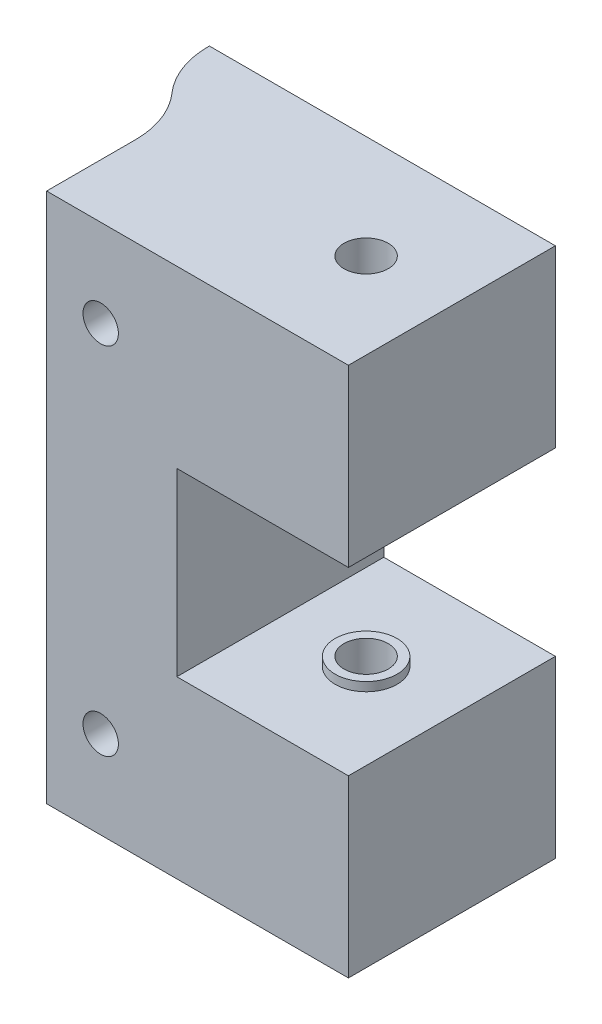
SolidWorks part; units mm, degrees
ref_plane "Front Plane" through (0, 0, 0) normal (0, 0, 1) x (1, 0, 0)
ref_plane "Top Plane" through (0, 0, 0) normal (0, 1, 0) x (1, 0, 0)
ref_plane "Right Plane" through (0, 0, 0) normal (1, 0, 0) x (0, 0, -1)
sketch "MainBlock" plane through (0, 0, 0) normal (0, 0, 1) x (1, 0, 0)
  line L0 (0, 0) -> (39.125, 0)
  line L1 (39.125, 0) -> (39.125, 19.8)
  line L2 (39.125, 19.8) -> (19.725, 19.8)
  line L3 (19.725, 19.8) -> (19.725, 40.2)
  line L4 (19.725, 40.2) -> (39.125, 40.2)
  line L5 (39.125, 40.2) -> (39.125, 60)
  line L6 (39.125, 60) -> (0, 60)
  line L7 (0, 60) -> (0, 0)
  circle A0 centre (11.1125, 50.1) radius 2
  circle A1 centre (11.1125, 9.9) radius 2
  dimension "D4" = 4
  dimension "D1" = 39.125
  dimension "D2" = 60
  dimension "D3" = 20.4
  dimension "D5" = 19.4
  dimension "D6" = 11.1125
  dimension "D7" = 9.9
  dimension "D8" = 9.9
extrude "MainBlockBoss-Extrude1" add sketch "MainBlock" along normal blind 23.4
sketch "TopHoleCut-Sketch2" plane through (0, 60, 0) normal (0, 1, 0) x (1, 0, 0)
  line L0 (39.125, 0) -> (0, 0) construction
  circle A0 centre (29.425, -11.7) radius 2.5
  dimension "D3" = 5
  dimension "D1" = 11.7
  dimension "D2" = 9.7
extrude "TopHoleCut-Extrude1" cut sketch "TopHoleCut-Sketch2" against normal blind 45
sketch "TopSpacerSketch4" plane through (0, 40.2, 0) normal (0, -1, 0) x (1, 0, 0)
  circle A0 centre (29.425, 11.7) radius 3.5
  circle A1 centre (29.425, 11.7) radius 2.5
  circle A2 centre (29.425, 11.7) radius 2.5 construction
  dimension "D1" = 7
extrude "TopSpacerBoss-Extrude2" add sketch "TopSpacerSketch4" along normal blind 1
sketch "LowerSpacerSketch5" plane through (0, 19.8, 0) normal (0, 1, 0) x (1, 0, 0)
  circle A0 centre (29.425, -11.7) radius 2.5
  circle A1 centre (29.425, -11.7) radius 2.5 construction
  circle A2 centre (29.425, -11.7) radius 3.5
  circle A3 centre (29.425, -11.7) radius 3.5 construction
extrude "LowerSpacerBoss-Extrude3" add sketch "LowerSpacerSketch5" along normal blind 1
sketch "MountHoleBoreSketch1" plane through (0, 0, 0) normal (0, 0, -1) x (-1, 0, 0)
  line L1 (-7.2375, 50.1) -> (-9.175, 53.4558)
  line L2 (-9.175, 53.4558) -> (-13.05, 53.4558)
  line L3 (-13.05, 53.4558) -> (-14.9875, 50.1)
  line L4 (-14.9875, 50.1) -> (-13.05, 46.7442)
  line L5 (-13.05, 46.7442) -> (-9.175, 46.7442)
  line L6 (-9.175, 46.7442) -> (-7.2375, 50.1)
  line L7 (-7.2375, 9.9) -> (-9.175, 13.2558)
  line L8 (-9.175, 13.2558) -> (-13.05, 13.2558)
  line L9 (-13.05, 13.2558) -> (-14.9875, 9.9)
  line L10 (-14.9875, 9.9) -> (-13.05, 6.5442)
  line L11 (-13.05, 6.5442) -> (-9.175, 6.5442)
  line L12 (-9.175, 6.5442) -> (-7.2375, 9.9)
  circle A0 centre (-11.1125, 50.1) radius 3.3558 construction
  circle A1 centre (-11.1125, 9.9) radius 3.3558 construction
  dimension "D1" = 7.75
extrude "MountHoleBoreCut-Extrude1" cut sketch "MountHoleBoreSketch1" against normal blind 2
sketch "PushPinHoleSketch1" plane through (0, 0, 0) normal (0, -1, 0) x (1, 0, 0)
  circle A0 centre (29.425, 11.7) radius 1
  circle A1 centre (29.425, 11.7) radius 2.5 construction
  dimension "D1" = 2
extrude "PushPinHoleCut-Extrude1" cut sketch "PushPinHoleSketch1" against normal through all
sketch "ScrewCollisionSketch1" plane through (0, 0, 0) normal (-1, 0, 0) x (0, 0, 1)
  line L0 (23.4, 60) -> (23.4, 0) construction
  line L1 (23.4, 60) -> (4.68, 60)
  line L2 (23.4, 60) -> (23.4, 0)
  line L3 (23.4, 0) -> (4.68, 0)
  line L4 (4.68, 60) -> (4.68, 0)
  line L5 (23.4, 0) -> (0, 0) construction
  line L6 (23.4, 60) -> (0, 60) construction
  dimension "D1" = 18.72
extrude "Cut-Extrude1" cut sketch "ScrewCollisionSketch1" against normal blind 5
fillet "Fillet1" radius 10 1 edges at (5, 30, 4.68)
fillet "Fillet2" radius 10 1 edges at (0, 30, 4.68)
sketch "MidRailInsetSketch1" plane through (0, 0, 0) normal (0, 0, -1) x (-1, 0, 0)
  line L0 (0, 60) -> (0, 0) construction
  line L1 (0, 40.4) -> (-3.18, 40.4)
  line L2 (0, 40.4) -> (0, 0)
  line L3 (0, 0) -> (-3.18, 0)
  line L4 (-3.18, 40.4) -> (-3.18, 0)
  line L6 (0, 0) -> (-39.125, 0) construction
  line L7 (-39.125, 60) -> (0, 60) construction
  dimension "D1" = 3.18
  dimension "D2" = 19.6
extrude "MidRailInsetCut-Extrude2" cut sketch "MidRailInsetSketch1" against normal through all
equation "\"BeltTensionerWidth\"= \"MidRailToAlignWithGantryBlock\" + \"BeltTensionerInnerWidth\" / 2 + \"RailThickness\""
equation "\"BeltTensionerHeight\"= 60mm"
equation "\"BeltTensionerDepth\"= \"BeltTensionerBackWallThickness\" + \"BeltTensionerInnerDepth\"'Equals 23.4"
equation "\"BeltTensionerInnerWidth\"= \"20TGT2PulleyDiameter\" + \"BeltTensionerSpaceBetweenPulleyAndWall\""
equation "\"BeltTensionerInnerHeight\"= \"20TGT2PulleyWidth\" * 2 + \"1mmSpacer\" * 3"
equation "\"BeltTensionerBackWallThickness\"= 4mm"
equation "\"BeltTensionerInnerDepth\"= \"20TGT2PulleyDiameter\" + \"BeltTensionerSpaceBetweenPulleyAndWall\""
equation "\"RailThickness\"= .125in'Spec"
equation "\"HoleOffsetFromEdge\"= \"RailThickness\" * 2.5"
equation "\"LinearGBWithRailDepth\"= 12.75mm'Spec"
equation "\"GABDistanceFromBackToFirstPulley\"= 13.5mm"
equation "\"MidRailToAlignWithGantryBlock\"= \"LinearGBWithRailDepth\" + \"GABDistanceFromBackToFirstPulley\"'All outside cogs must align"
equation "\"20TGT2PulleyDiameter\"= 17.9mm'Spec"
equation "\"BeltTensionerSpaceBetweenPulleyAndWall\"= 1.5mm"
equation "\"BeltTensionerMountingHoleDiameter\"= 4.0mm"
equation "\"BeltTensionerMountingHoleOffsetFromEdge\"= \"HoleOffsetFromEdge\""
equation "\"20TGT2PulleyWidth\"= 8.7mm'The STL of the Pulley in the diagram is a bit larger"
equation "\"1mmSpacer\"= 1mm"
equation "\"SteelShaft5mmHoleDiameter\"= 5mm"
equation "\"BeltTensionerMountingHoleOuterBoreDepth\"= 2mm"
equation "\"BeltTensionerMountingHoleOuterBoreDiameter\"= 7.75mm"
equation "\"7mmx1mmSpacerDiameter\"= 7mm"
equation "\"7mmx1mmSpacerHeight\"= 1mm"
equation "\"D1@MainBlock\" = \"BeltTensionerWidth\""
equation "\"D2@MainBlock\" = \"BeltTensionerHeight\""
equation "\"D3@MainBlock\" = \"BeltTensionerInnerHeight\""
equation "\"D4@MainBlock\" = \"BeltTensionerMountingHoleDiameter\""
equation "\"D5@MainBlock\" = \"BeltTensionerInnerWidth\""
equation "\"D6@MainBlock\"=\"BeltTensionerMountingHoleOffsetFromEdge\" + \"RailThickness\""
equation "\"D7@MainBlock\"=\"BeltTensionerMountingHoleOffstFromTopOrBottom\""
equation "\"D8@MainBlock\"=\"BeltTensionerMountingHoleOffstFromTopOrBottom\""
equation "\"D1@MainBlockBoss-Extrude1\" = \"BeltTensionerDepth\""
equation "\"D1@TopHoleCut-Sketch2\" = \"BeltTensionerDepth\" / 2"
equation "\"D3@TopHoleCut-Sketch2\" = \"SteelShaft5mmHoleDiameter\""
equation "\"D1@TopSpacerSketch4\" = \"7mmx1mmSpacerDiameter\""
equation "\"D1@TopSpacerBoss-Extrude2\" = \"7mmx1mmSpacerHeight\""
equation "\"D1@LowerSpacerBoss-Extrude3\" = \"7mmx1mmSpacerHeight\""
equation "\"D1@MountHoleBoreSketch1\" = \"BeltTensionerMountingHoleOuterBoreDiameter\""
equation "\"D1@MountHoleBoreCut-Extrude1\" = \"BeltTensionerMountingHoleOuterBoreDepth\""
equation "\"SteelPinPushHoleDiameter\"= 2mm"
equation "\"D1@PushPinHoleSketch1\" = \"SteelPinPushHoleDiameter\""
equation "\"D2@TopHoleCut-Sketch2\"=\"BeltTensionerWidth\" - \"MidRailToAlignWithGantryBlock\" - \"RailThickness\""
equation "\"BeltTensionerMountingHoleOffstFromTopOrBottom\"= ( \"BeltTensionerHeight\" - \"BeltTensionerInnerHeight\" ) / 4"
equation "\"BeltTensionerSteelShaftHoleDepthFromTop\"= ( \"SteelShaftLength\" - \"BeltTensionerInnerHeight\" ) / 2 + ( \"BeltTensionerHeight\" - \"BeltTensionerInnerHeight\" ) / 2 + \"BeltTensionerInnerHeight\"'Equals 45"
equation "\"SteelShaftLength\"= 30mm"
equation "\"D1@TopHoleCut-Extrude1\"=\"BeltTensionerSteelShaftHoleDepthFromTop\""
equation "\"D1@ScrewCollisionSketch1\" = \"BeltTensionerDepth\" * .8"
equation "\"MidLeftOrRightSideRailHeight\"= 2.0in"
equation "\"MidSideRailVerticalOffset\"= \"LinearRailWidth\" + 3mm'Allows space for RodStabilizer to attach to bottom of MidSideRail"
equation "\"LinearRailWidth\"= 12mm'Spec"
equation "\"D2@MidRailInsetSketch1\"=\"DistanceAboveMidSideRailToTopOfBeltTensioner\""
equation "\"DistanceAboveMidSideRailToTopOfBeltTensioner\"= \"MidSideRailVerticalOffset\" + \"BeltTensionerHeight\" / 2 - \"MidLeftOrRightSideRailHeight\" / 2"
